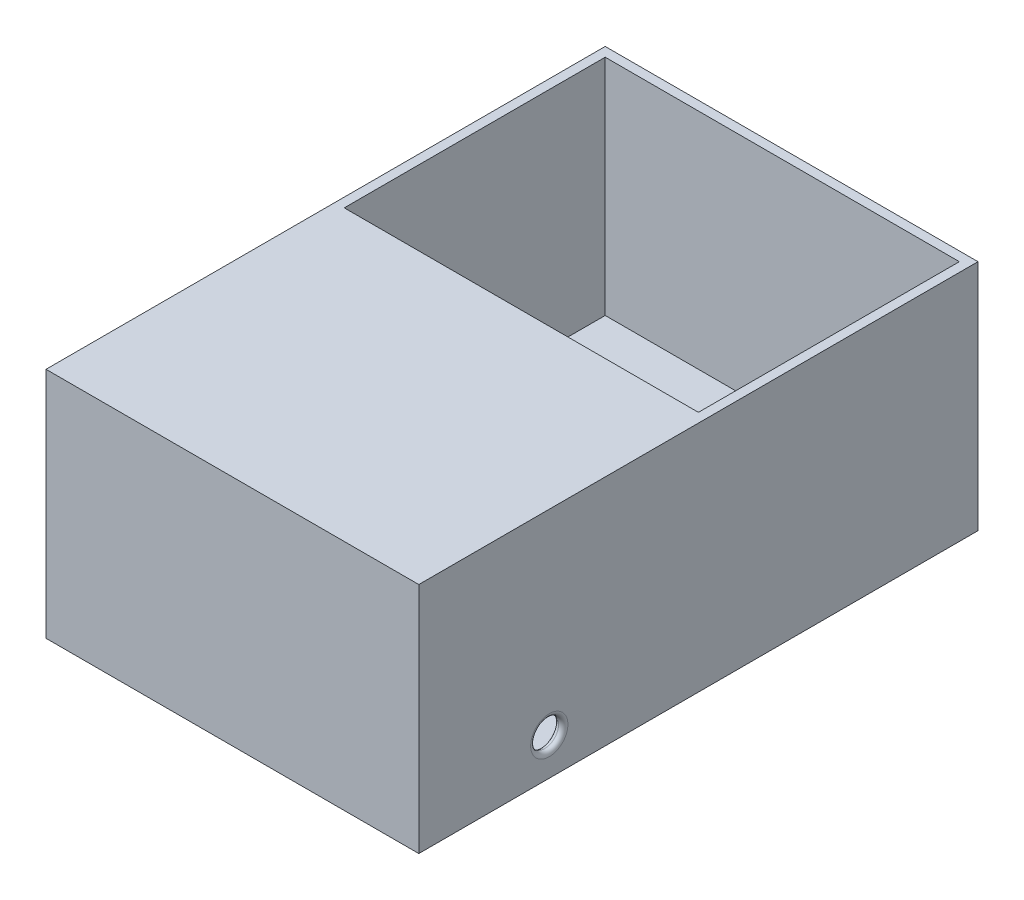
SolidWorks part; units mm, degrees
ref_plane "Front Plane" through (0, 0, 0) normal (0, 0, 1) x (1, 0, 0)
ref_plane "Top Plane" through (0, 0, 0) normal (0, 1, 0) x (1, 0, 0)
ref_plane "Right Plane" through (0, 0, 0) normal (1, 0, 0) x (0, 0, -1)
sketch "Sketch2" plane through (0, 0, 0) normal (0, 1, 0) x (1, 0, 0)
  line L1 (100, 150) -> (-100, 150)
  line L2 (100, 150) -> (100, -150)
  line L3 (100, -150) -> (-100, -150)
  line L4 (-100, 150) -> (-100, -150)
  line L5 (100, 150) -> (-100, -150) construction
  line L6 (100, -150) -> (-100, 150) construction
  point P0 (0, 0)
extrude "Boss-Extrude1" add sketch "Sketch2" along normal blind 5
sketch "Sketch4" plane through (0, 5, 0) normal (0, 1, 0) x (1, 0, 0)
  line L0 (-95, 145) -> (-95, -145)
  line L1 (100, 150) -> (-100, 150)
  line L2 (100, 150) -> (100, -150)
  line L3 (100, -150) -> (-100, -150)
  line L4 (-100, 150) -> (-100, -150)
  line L7 (95, -145) -> (-95, -145)
  line L8 (95, 145) -> (95, -145)
  line L9 (95, 145) -> (-95, 145)
  point P0 (0, 0)
  dimension "D1" = 5
extrude "Boss-Extrude2" add sketch "Sketch4" along normal blind 120
sketch "Sketch5" plane through (0, 0, 145) normal (0, 0, -1) x (-1, 0, 0)
  line L1 (-95, 125) -> (95, 125)
  line L2 (-95, 125) -> (-95, 120)
  line L3 (-95, 120) -> (95, 120)
  line L4 (95, 125) -> (95, 120)
extrude "Boss-Extrude3" add sketch "Sketch5" along normal blind 150
sketch "Sketch7" plane through (-95, 0, 0) normal (1, 0, 0) x (0, 0, -1)
  circle A0 centre (-80, 20) radius 7.5
extrude "Cut-Extrude1" cut sketch "Sketch7" against normal mid plane 430
fillet "Fillet4" radius 2.5 4 edges at (-95, 20, 72.5) (-100, 20, 72.5) (100, 20, 87.5) (95, 20, 87.5)
